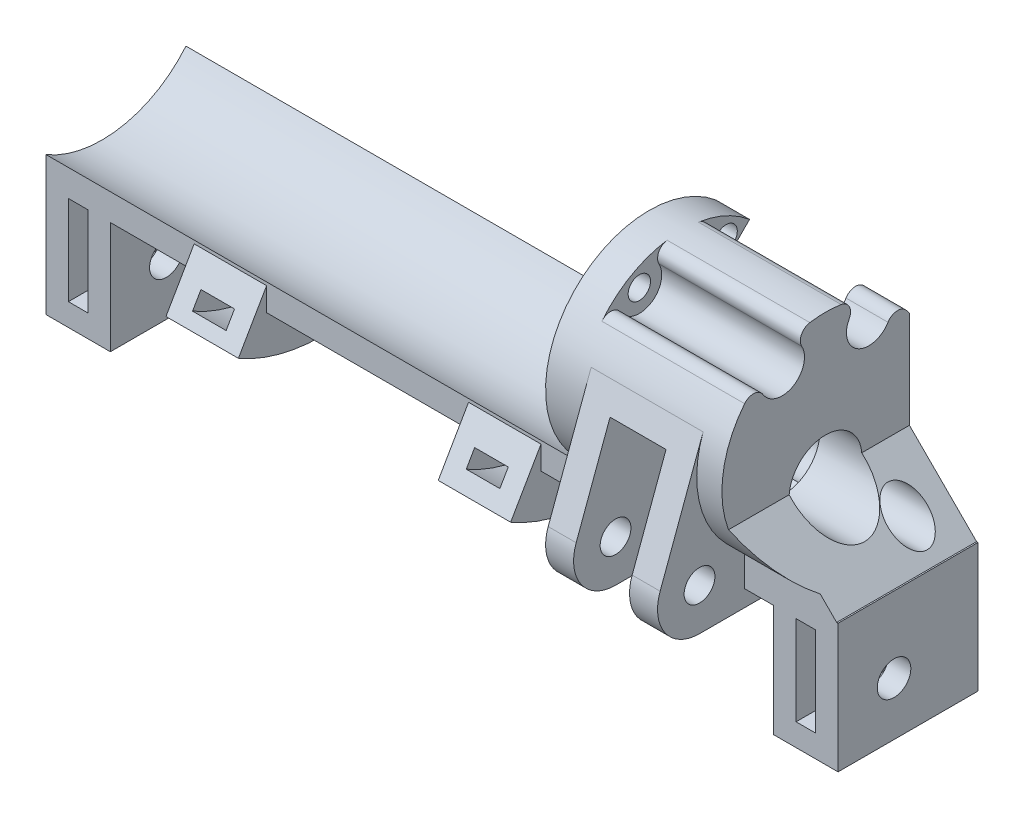
SolidWorks part; units mm, degrees
ref_plane "Front Plane" through (0, 0, 0) normal (0, 0, 1) x (1, 0, 0)
ref_plane "Top Plane" through (0, 0, 0) normal (0, 1, 0) x (1, 0, 0)
ref_plane "Right Plane" through (0, 0, 0) normal (1, 0, 0) x (0, 0, -1)
sketch "Sketch1" plane through (0, 0, 0) normal (0, 0, 1) x (1, 0, 0)
  line L0 (-59.25, 0) -> (59.25, 0)
  line L1 (59.25, 0) -> (59.25, -20)
  line L2 (59.25, -20) -> (70.75, -20)
  line L3 (70.75, -20) -> (70.75, 3)
  line L4 (70.75, 3) -> (-70.75, 3)
  line L5 (0, -55) -> (0, 55) construction
  line L6 (63.25, -0.032) -> (66.75, -0.032)
  line L7 (63.25, -0.032) -> (63.25, -16)
  line L8 (63.25, -16) -> (66.75, -16)
  line L9 (66.75, -0.032) -> (66.75, -16)
  line L10 (-66.75, -0.032) -> (-66.75, -16)
  line L11 (-63.25, -16) -> (-66.75, -16)
  line L12 (-63.25, -0.032) -> (-63.25, -16)
  line L13 (-63.25, -0.032) -> (-66.75, -0.032)
  line L14 (-70.75, -20) -> (-70.75, 3)
  line L15 (-59.25, -20) -> (-70.75, -20)
  line L16 (-59.25, 0) -> (-59.25, -20)
  point P4 (0, 0)
  point P13 (65, -20)
  point P14 (70.75, -8.5)
  point P22 (0, 3)
  dimension "D1" = 20
  dimension "D2" = 11.5
  dimension "D3" = 3
  dimension "D4" = 4
  dimension "D5" = 4
  dimension "D6" = 4
  dimension "D7" = 118.5
extrude "Boss-Extrude1" add sketch "Sketch1" against normal blind 15 and the other way blind 10
sketch "Sketch4" plane through (0, 0, 0) normal (1, 0, 0) x (0, 0, -1)
  line L0 (15, -20) -> (-10, -20) construction
  circle A0 centre (0, -10.5) radius 3
  point P6 (0, 0)
  dimension "D1" = 9.5
  dimension "D2" = 6
extrude "Cut-Extrude1" cut sketch "Sketch4" against normal through all both and the other way through all
sketch "Sketch5" plane through (0, 0, 0) normal (1, 0, 0) x (0, 0, -1)
  line L0 (0, -10.5) -> (0, 14.5) construction
  line L1 (0, 14.5) -> (0, 21.5) construction
  line L2 (0, 3) -> (-10, 3)
  line L3 (-10, 3) -> (-10, 5.9356)
  line L4 (15, 3) -> (15, 10.6718)
  line L5 (15, 3) -> (0, 3)
  line L6 (-10, -20) -> (-10, 3) construction
  circle A0 centre (0, 14.5) radius 6.5
  arc A1 (15, 10.6718) -> (-10, 5.9356) centre (0, 21.5) ccw
  dimension "D2" = 13
  dimension "D4" = 37
  dimension "D1" = 25
  dimension "D3" = 7
extrude "Boss-Extrude2" add sketch "Sketch5" along normal blind 31.5 from offset 27
sketch "Sketch11" plane through (27, 0, 0) normal (-1, 0, 0) x (0, 0, 1)
  circle A0 centre (0, 14.5) radius 9
  dimension "D1" = 18
extrude "Cut-Extrude6" cut sketch "Sketch11" against normal blind 18 from offset 6 offset against normal yes
sketch "Sketch8" plane through (27, 0, 0) normal (-1, 0, 0) x (0, 0, 1)
  line L7 (18, -10.5) -> (18, 4.5) construction
  line L8 (0, -10.5) -> (18, -10.5) construction
  line L9 (10, -3) -> (18, -3)
  line L10 (10, 12) -> (10, -3)
  line L11 (18, 12) -> (10, 12)
  circle A2 centre (18, 4.5) radius 2.75
  arc A3 (18, 12) -> (18, -3) centre (18, 4.5) cw
  point P0 (10, -8)
  dimension "D3" = 5.5
  dimension "D4" = 7.5
  dimension "D1" = 18
  dimension "D2" = 15
extrude "Boss-Extrude4" add sketch "Sketch8" against normal blind 20 from offset 7 offset against normal yes
sketch "Sketch13" plane through (34, 0, 0) normal (-1, 0, 0) x (0, 0, 1)
  line L0 (25.036, 7.097) -> (17.3555, 27.9059)
  line L1 (25.036, 7.097) -> (13.5588, 11.248)
  line L2 (13.5588, 11.248) -> (17.3555, 27.9059)
  arc A0 (18, -3) -> (18, 12) centre (18, 4.5) ccw construction
  arc A2 (10, 5.9356) -> (-15, 10.6718) centre (0, 21.5) ccw construction
extrude "Boss-Extrude5" add sketch "Sketch13" along direction (1, 0, 0) on the side against the normal up to surface (20 mm away) up to face at (54, 3.9327, 14.9542)
chamfer "Chamfer3" distance 8 angle 45 1 edges at (44, 0, 10)
sketch "Sketch12" plane through (27, 0, 0) normal (-1, 0, 0) x (0, 0, 1)
  line L0 (9.5, 4.5) -> (9.5, 5.5)
  line L1 (9.5, 5.5) -> (0, 5.5)
  line L2 (0, 5.5) -> (0, 23.5)
  line L3 (0, 23.5) -> (26.5, 23.5)
  line L4 (26.5, 23.5) -> (26.5, 4.5)
  arc A0 (9.5, 4.5) -> (26.5, 4.5) centre (18, 4.5) ccw
  circle A1 centre (0, 14.5) radius 9 construction
  dimension "D1" = 17
extrude "Cut-Extrude7" cut sketch "Sketch12" against normal blind 10 from offset 12 offset against normal yes
sketch "Sketch14" plane through (27, 0, 0) normal (-1, 0, 0) x (0, 0, 1)
  line L0 (0, 14.5) -> (-20.9663, 35.4663) construction
  line L1 (4.5962, 19.0962) -> (-16.3701, 40.0625)
  line L2 (-4.5962, 9.9038) -> (-25.5625, 30.8701)
  line L3 (4.5962, 19.0962) -> (-4.5962, 9.9038)
  line L4 (-25.5625, 30.8701) -> (-16.3701, 40.0625)
  dimension "D1" = 6.5
  dimension "D2" = 6.5
extrude "Cut-Extrude8" cut sketch "Sketch14" against normal blind 21
sketch "Sketch15" plane through (33, 0, 0) normal (1, 0, 0) x (0, 0, -1)
  line L0 (0, 14.5) -> (20.576, 35.076) construction
  line L1 (6.364, 8.136) -> (26.94, 28.7121)
  line L2 (-6.364, 20.864) -> (14.2121, 41.44)
  line L3 (-6.364, 20.864) -> (6.364, 8.136)
  line L4 (14.2121, 41.44) -> (26.94, 28.7121)
  dimension "D1" = 9
  dimension "D2" = 9
extrude "Cut-Extrude9" cut sketch "Sketch15" along normal up to surface (18 mm away) up to face at (51, 14.5, 6.5)
sketch "Sketch16" plane through (27, 0, 0) normal (-1, 0, 0) x (0, 0, 1)
  line L1 (-15, 3) -> (10, 3)
  line L2 (-15, 3) -> (-15, 15)
  line L3 (-15, 15) -> (10, 15)
  line L4 (10, 3) -> (10, 15)
  dimension "D1" = 12
  dimension "D2" = 25
extrude "Boss-Extrude6" add sketch "Sketch16" along normal up to surface (97.75 mm away) up to face at (-70.75, -10.5, -3)
sketch "Sketch10" plane through (27, 0, 0) normal (1, 0, 0) x (0, 0, -1)
  circle A0 centre (0, 21.5) radius 19.5
  dimension "D1" = 39
extrude "Cut-Extrude5" cut sketch "Sketch10" against normal through all
chamfer "Chamfer4" distance 12 angle 45 1 edges at (58.5, 3, -2.5)
sketch "Sketch6" plane through (0, 0, 0) normal (1, 0, 0) x (0, 0, -1)
  line L0 (0, 21.5) -> (15.5, 21.5) construction
  circle A0 centre (0, 21.5) radius 18.5 construction
  circle A1 centre (15.5, 21.5) radius 2
  circle A7 centre (7.75, 8.0766) radius 2
  circle A8 centre (-7.75, 8.0766) radius 2
  circle A9 centre (-15.5, 21.5) radius 2
  circle A10 centre (-7.75, 34.9234) radius 2
  circle A11 centre (7.75, 34.9234) radius 2
  dimension "D1" = 15.5
  dimension "D2" = 4
  dimension "D3" = 6
extrude "Cut-Extrude2" cut sketch "Sketch6" along normal through all contours A10 | A11 | A7
sketch "Sketch17" plane through (33, 0, 0) normal (1, 0, 0) x (0, 0, -1)
  circle A0 centre (7.75, 34.9234) radius 4
  circle A1 centre (-7.75, 34.9234) radius 4
  circle A3 centre (7.75, 8.0766) radius 3.5
  dimension "D1" = 8
  dimension "D2" = 8
  dimension "D4" = 7
extrude "Cut-Extrude10" cut sketch "Sketch17" along normal through all
sketch "Sketch19" plane through (0, 0, 0) normal (0, 0, 1) x (1, 0, 0)
  line L0 (14.3108, 21.5) -> (-40.9354, 21.5) construction
  line L1 (-70.75, 2) -> (27, 2) construction
  line L3 (-40.7048, -3.2287) -> (-34.7048, -3.2287)
  line L4 (-40.7048, -3.2287) -> (-40.7048, -6.2287)
  line L5 (-40.7048, -6.2287) -> (-34.7048, -6.2287)
  line L6 (-34.7048, -3.2287) -> (-34.7048, -6.2287)
  line L8 (14.1954, -3.2287) -> (8.1954, -3.2287)
  line L9 (14.1954, -3.2287) -> (14.1954, -6.2287)
  line L10 (14.1954, -6.2287) -> (8.1954, -6.2287)
  line L11 (8.1954, -3.2287) -> (8.1954, -6.2287)
  line L12 (-44.2832, -8.5717) -> (-31.3431, -8.5717)
  line L13 (-44.2832, -8.5717) -> (-44.2832, 2)
  line L14 (-44.2832, 2) -> (-31.3431, 2)
  line L15 (-31.3431, -8.5717) -> (-31.3431, 2)
  line L17 (4.7369, 2) -> (17.677, 2)
  line L18 (4.7369, 2) -> (4.7369, -9.3334)
  line L19 (4.7369, -9.3334) -> (17.677, -9.3334)
  line L20 (17.677, 2) -> (17.677, -9.3334)
  dimension "D1" = 19.5
  dimension "D2" = 3
  dimension "D3" = 6
  dimension "D4" = 3
  dimension "D5" = 6
revolve "Revolve1" add sketch "Sketch19" angle 30 about L0 other way angle 40
sketch "Sketch18" plane through (0, 0, 0) normal (1, 0, 0) x (0, 0, -1)
  line L1 (15, -6.8625) -> (21.1545, -6.8625)
  line L2 (15, -6.8625) -> (15, 37.4548)
  line L3 (15, 37.4548) -> (21.1545, 37.4548)
  line L4 (21.1545, -6.8625) -> (21.1545, 37.4548)
extrude "Cut-Extrude11" cut sketch "Sketch18" against normal through all both and the other way through all
fillet "Fillet1" radius 2 4 edges at (54.75, 35.8851, -11.6327) (45.75, 35.8851, 11.6327) (45.75, 38.7667, 6.6415) (45.75, 38.7667, -6.6415)
equation "\"D1@Sketch19\"=39/2"
